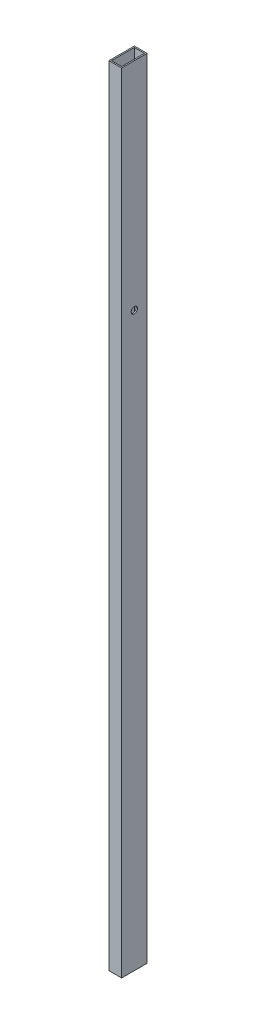
SolidWorks part; units mm, degrees
ref_plane "Спереди" through (0, 0, 0) normal (0, 0, 1) x (1, 0, 0)
ref_plane "Сверху" through (0, 0, 0) normal (0, 1, 0) x (1, 0, 0)
ref_plane "Справа" through (0, 0, 0) normal (1, 0, 0) x (0, 0, -1)
sketch "Эскиз1" plane through (0, 0, 0) normal (0, 1, 0) x (1, 0, 0)
  line L1 (-10, 20) -> (10, 20)
  line L2 (-10, 20) -> (-10, -20)
  line L3 (-10, -20) -> (10, -20)
  line L4 (10, 20) -> (10, -20)
  line L5 (-10, 20) -> (10, -20) construction
  line L6 (-10, -20) -> (10, 20) construction
  point P0 (0, 0)
extrude "Вытянуть-Тонкостенный1" add sketch "Эскиз1" along normal blind 1240 thin thin type one direction reverse wall 2
sketch "Эскиз2" plane through (10, 0, 0) normal (1, 0, 0) x (0, 0, -1)
  circle A0 centre (0, 900) radius 5
extrude "Вырез-Вытянуть1" cut sketch "Эскиз2" against normal through all
sketch "Эскиз3" plane through (-10, 0, 0) normal (-1, 0, 0) x (0, 0, 1)
  circle A0 centre (0, 860) radius 5
  circle A1 centre (0, 720) radius 5
  circle A2 centre (0, 580) radius 5
  dimension "D1" = 3
extrude "Вырез-Вытянуть2" cut sketch "Эскиз3" against normal blind 10
